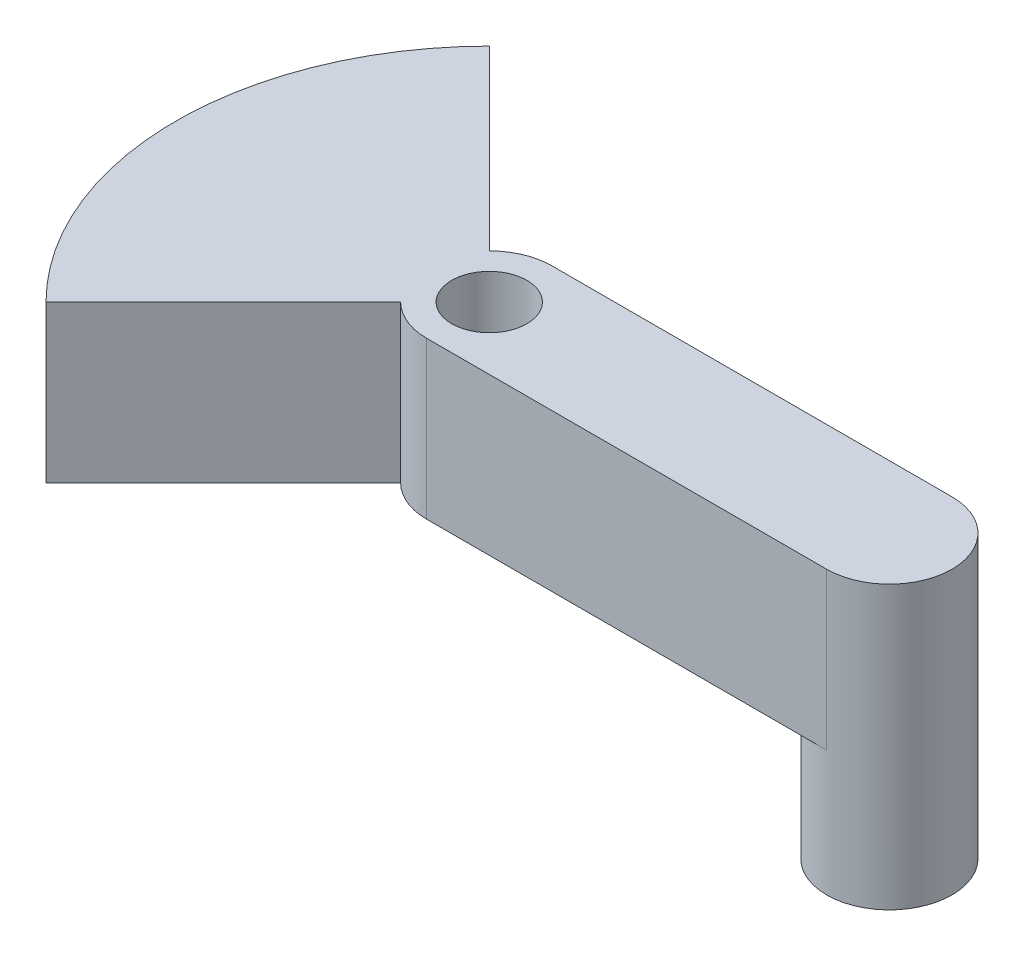
SolidWorks part; units mm, degrees
ref_plane "前视基准面" through (0, 0, 0) normal (0, 0, 1) x (1, 0, 0)
ref_plane "上视基准面" through (0, 0, 0) normal (0, 1, 0) x (1, 0, 0)
ref_plane "右视基准面" through (0, 0, 0) normal (1, 0, 0) x (0, 0, -1)
other "Configuration Table"
sketch "草图2" plane through (0, 0, 0) normal (0, 1, 0) x (1, 0, 0)
  line L0 (0, 0) -> (63.82, 0)
  line L1 (0, 0) -> (-50, 0)
  line L2 (-41.4519, 27.9596) -> (0, 0)
  line L3 (-41.4519, -27.9596) -> (0, 0)
  line L4 (0, 10) -> (63.82, 10)
  line L5 (63.82, 10) -> (63.82, -10)
  line L6 (63.82, -10) -> (0, -10)
  circle A0 centre (0, 0) radius 50
  circle A1 centre (63.82, 0) radius 10
  circle A2 centre (0, 0) radius 10
  arc A3 (-50, 0) -> (-41.4519, 27.9596) centre (0, 0) cw
  circle A4 centre (0, 0) radius 6
extrude "凸台-拉伸1" add sketch "草图2" along normal blind 25 contours A2 L2 A0 L1 | A2 L1 A0 L3 | A4 L2 A2 L1 | A4 L1 A2 L3 | A4 L3 A2 L0 | A4 L0 A2 L2 | A2 L0 A0 L4 | A2 L6 A0 L0 | A1 L0 A0 L6 | A1 L4 A0 L0 region at (1.7922, 0, -5.8619) region at (1.7922, 0, 5.8619) region at (-7.6957, 0, 2.3528) region at (-7.6957, 0, -2.3528) region at (28.7008, 0, -5.1219) region at (28.7008, 0, 5.1219) region at (-32.4582, 0, 9.9235) region at (-32.4582, 0, -9.9235) region at (53.2034, 0, -6.0754) region at (53.2034, 0, 6.0754)
extrude "凸台-拉伸2" add sketch "草图2<3>" along normal blind 25 and the other way blind 20 contours L5 A1 L0 | L0 A1 L5 | L5 A1 region at (59.5759, 0, -4.2441) region at (59.5759, 0, 4.2441) region at (68.0641, 0, 0)
sketch "草图2<3>" plane through (0, 0, 0) normal (0, 1, 0) x (1, 0, 0) same geometry as "草图2"
sketch "草图3" plane through (0, 25, 0) normal (0, 1, 0) x (1, 0, 0)
  line L0 (0, 0) -> (-35.3553, 35.3553)
  line L1 (0, 0) -> (-35.3553, -35.3553)
  circle A0 centre (0, 0) radius 50
  arc M5 (0, 10) -> (-8.2904, 5.5919) centre (0, 0) ccw
  line M6 (-8.2904, 5.5919) -> (-41.4519, 27.9596)
  line M8 (-41.4519, -27.9596) -> (-8.2904, -5.5919)
  arc M9 (-8.2904, -5.5919) -> (0, -10) centre (0, 0) ccw
extrude "凸台-拉伸3" add sketch "草图3" against normal blind 25 contours A0 L1 M8 M9 | L0 A0 M6 M5 region at (-26.5374, 25, -21.8757) region at (-26.5374, 25, 21.8757)
